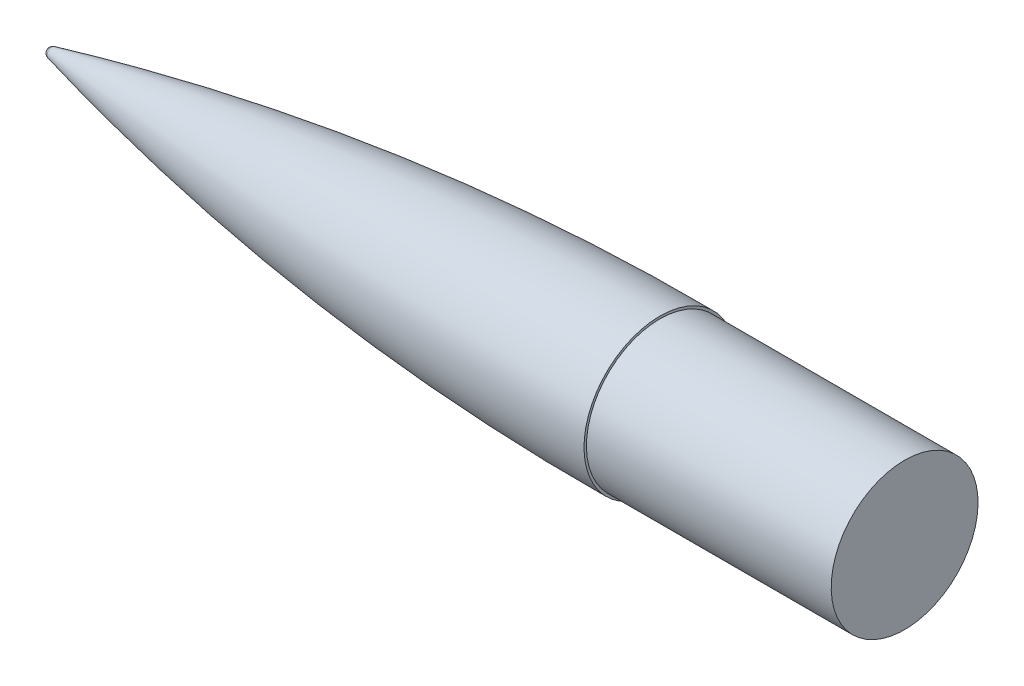
SolidWorks part; units mm, degrees
ref_plane "Front Plane" through (0, 0, 0) normal (0, 0, 1) x (1, 0, 0)
ref_plane "Top Plane" through (0, 0, 0) normal (0, 1, 0) x (1, 0, 0)
ref_plane "Right Plane" through (0, 0, 0) normal (1, 0, 0) x (0, 0, -1)
sketch "Sketch1" plane through (0, 0, 0) normal (0, 0, 1) x (1, 0, 0)
  line L0 (0, 0) -> (325.525, 0) construction
  line L1 (325.525, 0) -> (325.525, 39.37) construction
  line L2 (8.025, 0) -> (8.025, 30.9534) construction
  line L3 (452.525, 0) -> (8.025, 0)
  line L4 (325.525, 38.1) -> (452.525, 38.1)
  line L5 (452.525, 38.1) -> (452.525, 0)
  line L6 (325.525, 38.1) -> (325.525, 39.37)
  arc A1 (9.9641, 2.4679) -> (8.025, 0) centre (10.565, 0) ccw
  arc A2 (325.525, 39.37) -> (9.9641, 2.4679) centre (317.6933, -1261.3375) ccw
  arc A3 (13.105, 0) -> (9.9641, 2.4679) centre (10.565, 0) ccw construction
  arc A4 (8.025, 0) -> (13.105, 0) centre (10.565, 0) ccw construction
  arc A5 (8.025, 1.9942) -> (0, 0) centre (317.6933, -1261.3375) ccw construction
  arc A6 (9.9641, 2.4679) -> (8.025, 1.9942) centre (317.6933, -1261.3375) ccw construction
  point P4 (10.565, 0)
  point P5 (9.9641, 2.4679)
  point P11 (8.025, 0)
  dimension "D1" = 39.37
  dimension "D2" = 10.565
  dimension "D3" = 2.4679
  dimension "D4" = 9.9641
  dimension "D5" = 317.5
  dimension "D6" = 38.1
  dimension "D7" = 127
revolve "Revolve2" add sketch "Sketch1" angle 360 about L3
equation "\"r_n\"= 0.1'nose tip radius"
equation "\"R_nc\"= 3.1 / 2'nosecone base radius"
equation "\"L_nc\"= 12.5'exposed length of the nosecone"
equation "\"rho\"= ( \"R_nc\" ^ 2 + \"L_nc\" ^ 2 ) / ( 2 * \"R_nc\" )'ogive radius"
equation "\"x_0\"= \"L_nc\" - sqr ( ( \"rho\" - \"r_n\" ) ^ 2 - ( \"rho\" - \"R_nc\" ) ^ 2 )'center of tip sphere"
equation "\"y_t\"= \"r_n\" * ( \"rho\" - \"R_nc\" ) / ( \"rho\" - \"r_n\" )'y-coordinate of tangency point"
equation "\"x_t\"= \"x_0\" - sqr ( \"r_n\" ^ 2 - \"y_t\" ^ 2 )'x-coordinate of tangency point"
equation "\"x_a\"= \"x_0\" - \"r_n\"'apex point"
equation "\"D1@Sketch1\"=\"R_nc\""
equation "\"D2@Sketch1\"=\"x_0\""
equation "\"D3@Sketch1\"=\"y_t\""
equation "\"D4@Sketch1\"=\"x_t\""
equation "\"D5@Sketch1\"=\"L_nc\""
equation "\"t_nc\"= 3 / 32'wall thickness of nosecone"
equation "\"L_s\"= 5'length of shoulder"
equation "\"R_s\"= 3 / 2'radius of shoulder"
equation "\"t_s\"= 3 / 32'wall thickness of shoulder"
equation "\"D6@Sketch1\"=\"R_s\""
equation "\"D7@Sketch1\"=\"L_s\""
